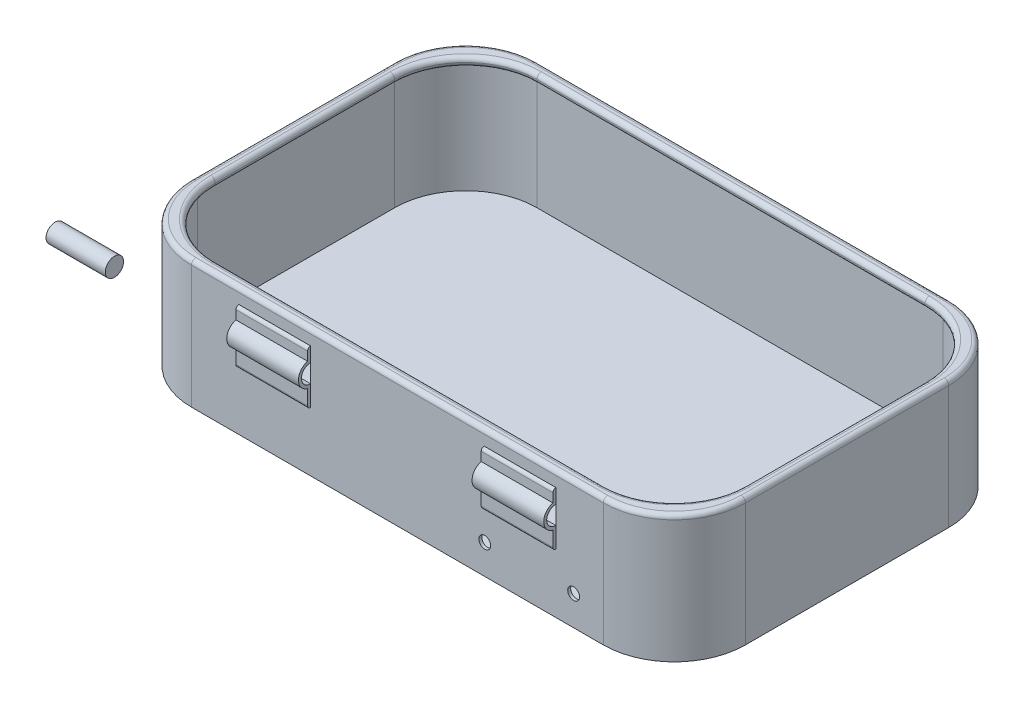
SolidWorks part; units mm, degrees
material "AISI 1010 Steel, hot rolled bar"
ref_plane "Front Plane" through (0, 0, 0) normal (0, 0, 1) x (1, 0, 0)
ref_plane "Top Plane" through (0, 0, 0) normal (0, 1, 0) x (1, 0, 0)
ref_plane "Right Plane" through (0, 0, 0) normal (1, 0, 0) x (0, 0, -1)
sketch "Sketch1" plane through (0, 0, 0) normal (0, 1, 0) x (1, 0, 0)
  line L0 (-46.75, 29.15) -> (46.75, -29.15) construction
  line L1 (-46.75, -29.15) -> (46.75, -29.15)
  line L2 (-46.75, -29.15) -> (-46.75, 29.15)
  line L3 (-46.75, 29.15) -> (46.75, 29.15)
  line L4 (46.75, -29.15) -> (46.75, 29.15)
  point P4 (0, 0)
  dimension "D1" = 93.5
  dimension "D2" = 58.3
extrude "Boss-Extrude1" add sketch "Sketch1" along normal blind 0.5
sketch "Sketch2" plane through (0, 0.5, 0) normal (0, 1, 0) x (1, 0, 0)
  line L4 (-46.25, -28.65) -> (46.25, -28.65)
  line L5 (46.25, -28.65) -> (46.25, 28.65)
  line L6 (46.25, 28.65) -> (-46.25, 28.65)
  line L7 (-46.25, 28.65) -> (-46.25, -28.65)
  line L8 (-46.75, -29.15) -> (46.75, -29.15)
  line L9 (-46.75, 29.15) -> (-46.75, -29.15)
  line L10 (46.75, -29.15) -> (46.75, 29.15)
  line L11 (46.75, 29.15) -> (-46.75, 29.15)
  line L12 (-46.75, -29.15) -> (46.75, -29.15)
  line L13 (-46.75, 29.15) -> (-46.75, -29.15)
  line L14 (46.75, -29.15) -> (46.75, 29.15)
  line L15 (46.75, 29.15) -> (-46.75, 29.15)
  dimension "D1" = 0
  dimension "D2" = 0.5
extrude "Boss-Extrude2" add sketch "Sketch2" along normal blind 21
sketch "Sketch3" plane through (0, 21.5, 0) normal (0, 1, 0) x (1, 0, 0)
  line L4 (-46.25, -28.65) -> (46.25, -28.65)
  line L5 (46.25, -28.65) -> (46.25, 28.65)
  line L6 (46.25, 28.65) -> (-46.25, 28.65)
  line L7 (-46.25, 28.65) -> (-46.25, -28.65)
  line L8 (-44.75, -27.15) -> (44.75, -27.15)
  line L9 (44.75, -27.15) -> (44.75, 27.15)
  line L10 (44.75, 27.15) -> (-44.75, 27.15)
  line L11 (-44.75, 27.15) -> (-44.75, -27.15)
  line L12 (-44.75, -27.15) -> (44.75, -27.15)
  line L13 (44.75, -27.15) -> (44.75, 27.15)
  line L14 (44.75, 27.15) -> (-44.75, 27.15)
  line L15 (-44.75, 27.15) -> (-44.75, -27.15)
  dimension "D1" = 1.5
  dimension "D2" = 1.5
extrude "Boss-Extrude3" add sketch "Sketch3" against normal blind 1.5
fillet "Fillet2" radius 12 12 edges at (-46.75, 10.75, -29.15) (-44.75, 20.75, -27.15) (-46.25, 10.25, -28.65) (-46.75, 10.75, 29.15) (-46.25, 10.25, 28.65) (-44.75, 20.75, 27.15) (44.75, 20.75, 27.15) (46.25, 10.25, 28.65) (46.75, 10.75, 29.15) (46.25, 10.25, -28.65) (44.75, 20.75, -27.15) (46.75, 10.75, -29.15)
fillet "Fillet3" radius 0.749 24 edges at (-41.2353, 20, 23.6353) (-44.75, 20, 0) (-41.2353, 20, -23.6353) (0, 20, -27.15) (41.2353, 20, -23.6353) (44.75, 20, 0) (41.2353, 20, 23.6353) (-41.2353, 21.5, 23.6353) (-44.75, 21.5, 0) (-41.2353, 21.5, -23.6353) (0, 21.5, -27.15) (41.2353, 21.5, -23.6353) (44.75, 21.5, 0) (41.2353, 21.5, 23.6353) (0, 20, 27.15) (0, 21.5, 27.15) (-43.2353, 21.5, 25.6353) (-46.75, 21.5, 0) (-43.2353, 21.5, -25.6353) (0, 21.5, -29.15) (43.2353, 21.5, -25.6353) (46.75, 21.5, 0) (43.2353, 21.5, 25.6353) (0, 21.5, 29.15)
sketch "Sketch4" plane through (0, 0, 28.65) normal (0, 0, -1) x (-1, 0, 0)
  line L0 (-34.75, 21.5) -> (34.75, 21.5) construction
  line L1 (-26.75, 10) -> (-14.65, 10)
  line L2 (-26.75, 10) -> (-26.75, 19)
  line L3 (-26.75, 19) -> (-14.65, 19)
  line L4 (-14.65, 10) -> (-14.65, 19)
  line L5 (14.65, 10) -> (26.75, 10)
  line L6 (14.65, 10) -> (14.65, 19)
  line L7 (14.65, 19) -> (26.75, 19)
  line L8 (26.75, 10) -> (26.75, 19)
  line L9 (-34.75, 20.751) -> (-34.75, 0) construction
  line L10 (34.75, 0) -> (34.75, 20.751) construction
  dimension "D1" = 12.1
  dimension "D2" = 9
  dimension "D3" = 2.5
  dimension "D4" = 8
  dimension "D5" = 8
extrude "Cut-Extrude1" cut sketch "Sketch4" against normal up to surface (0.5 mm away) up to face at (0, 10.3755, 29.15)
sketch "Sketch5" plane through (-46.75, 0, 0) normal (-1, 0, 0) x (0, 0, 1)
  line L0 (29.15, 20.751) -> (29.15, 0) construction
  line L2 (29.65, 17) -> (29.65, 19)
  line L3 (29.65, 19) -> (29.15, 19)
  line L4 (29.15, 19) -> (29.15, 16.5619)
  line L5 (29.15, 13.4619) -> (29.15, 10)
  line L6 (29.15, 10) -> (29.65, 10)
  line L7 (29.65, 10) -> (29.65, 13.0238)
  arc A0 (29.15, 13.4619) -> (29.15, 16.5619) centre (29.15, 15.0119) ccw
  arc A1 (29.65, 13.0238) -> (29.65, 17) centre (29.15, 15.0119) ccw
  arc A2 (29.15, 12.9619) -> (29.15, 17.0619) centre (29.15, 15.0119) ccw construction
  dimension "D1" = 1.55
  dimension "D3" = 0.5
  dimension "D4" = 2
  dimension "D2" = 0.5
extrude "Boss-Extrude4" add sketch "Sketch5" against normal up to surface (32.1 mm away) from surface separate body up to face at (-14.65, 14.5, 28.9) starting at face at (-26.75, 14.5, 28.9)
extrude "Boss-Extrude5" add sketch "Sketch5<2>" against normal up to surface (73.5 mm away) from surface separate body up to face at (26.75, 14.5, 28.9) starting at face at (14.65, 14.5, 28.9)
sketch "Sketch5<2>" plane through (-46.75, 0, 0) normal (-1, 0, 0) x (0, 0, 1) same geometry as "Sketch5"
fillet "Fillet4" radius 0.5 2 edges at (-20.7, 10, 29.65) (-20.7, 19, 29.65)
fillet "Fillet5" radius 0.5 2 edges at (20.7, 10, 29.65) (20.7, 19, 29.65)
sketch "Sketch6" plane through (-46.75, 0, 0) normal (-1, 0, 0) x (0, 0, 1)
  line L0 (30.15, 15.0119) -> (29.15, 15.0119) construction
  circle A0 centre (30.15, 15.0119) radius 1.55
  dimension "D1" = 3.1
  dimension "D2" = 1
extrude "Boss-Extrude6" add sketch "Sketch6" along normal blind 10 separate body
sketch "Sketch7" plane through (0, 0, 29.15) normal (0, 0, 1) x (1, 0, 0)
  line L0 (14.75, 5) -> (29.75, 5) construction
  line L1 (34.75, 0) -> (34.75, 20.751) construction
  line L2 (-34.75, 0) -> (34.75, 0) construction
  circle A0 centre (14.75, 5) radius 1
  circle A1 centre (29.75, 5) radius 1
  dimension "D1" = 2
  dimension "D3" = 5
  dimension "D2" = 15
  dimension "D4" = 5
extrude "Cut-Extrude2" cut sketch "Sketch7" against normal up to surface (0.5 mm away) up to face at (20.7, 14.5, 28.65)
